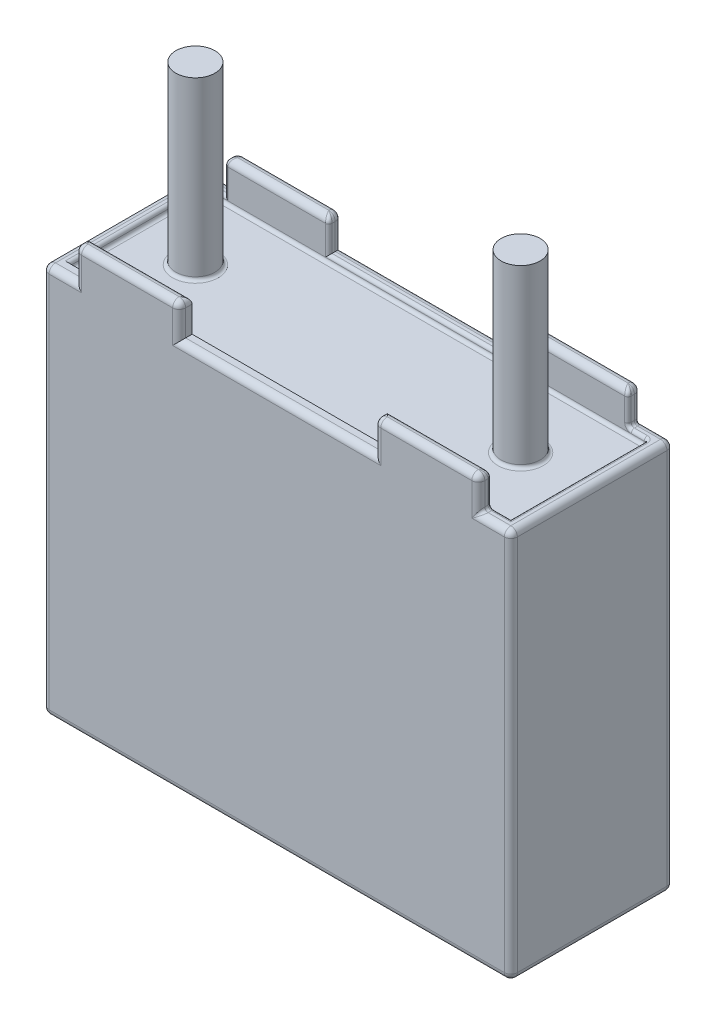
SolidWorks part; units mm, degrees
material "Sade Karbon Çeliği"
ref_plane "Ön Düzlem" through (0, 0, 0) normal (0, 0, 1) x (1, 0, 0)
ref_plane "Üst Düzlem" through (0, 0, 0) normal (0, 1, 0) x (1, 0, 0)
ref_plane "Sağ Düzlem" through (0, 0, 0) normal (1, 0, 0) x (0, 0, -1)
sketch "Çizim1" plane through (0, 0, 0) normal (0, 1, 0) x (1, 0, 0)
  line L1 (-3.6, -1.25) -> (3.6, -1.25)
  line L2 (-3.6, -1.25) -> (-3.6, 1.25)
  line L3 (-3.6, 1.25) -> (3.6, 1.25)
  line L4 (3.6, -1.25) -> (3.6, 1.25)
  line L5 (-3.6, -1.25) -> (3.6, 1.25) construction
  line L6 (-3.6, 1.25) -> (3.6, -1.25) construction
  point P0 (0, 0)
  dimension "D1" = 7.2
  dimension "D2" = 2.5
extrude "Тяло" add sketch "Çizim1" against normal blind 6.5
sketch "Çizim2" plane through (0, 0, 0) normal (0, 1, 0) x (1, 0, 0)
  line L0 (-3.6, 1.25) -> (-3.6, -1.25) construction
  line L1 (3.4, -1.05) -> (-3.4, -1.05)
  line L2 (3.4, -1.05) -> (3.4, 1.05)
  line L3 (3.4, 1.05) -> (-3.4, 1.05)
  line L4 (-3.4, -1.05) -> (-3.4, 1.05)
  line L5 (3.4, -1.05) -> (-3.4, 1.05) construction
  line L6 (3.4, 1.05) -> (-3.4, -1.05) construction
  line L7 (-3.6, -1.25) -> (3.6, -1.25) construction
  point P0 (0, 0)
  dimension "D1" = 0.2
  dimension "D2" = 0.2
extrude "Kes-Ekstrüzyon1" cut sketch "Çizim2" against normal blind 0.6
sketch "Çizim3" plane through (0, 0, 1.25) normal (0, 0, 1) x (1, 0, 0)
  line L2 (1.5, -0.5) -> (-1.5, -0.5)
  line L3 (1.5, -0.5) -> (1.5, 0)
  line L4 (-1.5, -0.5) -> (-1.5, 0)
  line L5 (1.5, 0) -> (-1.5, 0)
  line L7 (1.5, -0.5) -> (-1.5, 0) construction
  line L9 (-1.5, -0.5) -> (1.5, 0) construction
  line L10 (-3.6, 0) -> (3.6, 0) construction
  line L12 (-3.6, 0) -> (-3.1, 0)
  line L13 (-3.6, 0) -> (-3.6, -0.5)
  line L14 (-3.6, -0.5) -> (-3.1, -0.5)
  line L15 (-3.1, 0) -> (-3.1, -0.5)
  line L16 (3.6, 0) -> (3.1, 0)
  line L17 (3.6, 0) -> (3.6, -0.5)
  line L18 (3.6, -0.5) -> (3.1, -0.5)
  line L19 (3.1, 0) -> (3.1, -0.5)
  point P1 (0, -0.25)
  dimension "D1" = 0.5
  dimension "D2" = 3
  dimension "D3" = 0.5
extrude "Kes-Ekstrüzyon2" cut sketch "Çizim3" against normal blind 7
sketch "Çizim4" plane through (0, -0.6, 0) normal (0, 1, 0) x (-1, 0, 0)
  line L0 (-2.5, 0) -> (2.5, 0) construction
  circle A0 centre (-2.5, 0) radius 0.3
  circle A1 centre (2.5, 0) radius 0.3
  point P1 (0, 0)
  dimension "D1" = 5
  dimension "D2" = 0.6
extrude "Pin" add sketch "Çizim4" along normal blind 2.7
fillet "Radyus1" radius 0.1 40 edges at (0, -6.5, -1.25) (-3.6, -6.5, 0) (0, -6.5, 1.25) (3.6, -6.5, 0) (3.6, -0.5, 0) (-1.5, -0.25, 1.25) (0, -0.5, 1.25) (1.5, -0.25, 1.25) (3.1, -0.25, 1.25) (3.35, -0.5, 1.25) (3.6, -3.5, 1.25) (-3.35, -0.5, 1.25) (-3.1, -0.25, 1.25) (-3.6, -3.5, 1.25) (-3.6, -0.5, 0) (-3.35, -0.5, -1.25) (-3.6, -3.5, -1.25) (3.6, -3.5, -1.25) (3.35, -0.5, -1.25) (3.1, -0.25, -1.25) (1.5, -0.25, -1.25) (0, -0.5, -1.25) (-1.5, -0.25, -1.25) (-3.1, -0.25, -1.25) (-1.5, 0, 1.15) (-2.3, 0, 1.25) (-3.1, 0, 1.15) (-2.3, 0, 1.05) (3.1, 0, -1.15) (2.3, 0, -1.05) (1.5, 0, -1.15) (2.3, 0, -1.25) (3.1, 0, 1.15) (2.3, 0, 1.25) (1.5, 0, 1.15) (2.3, 0, 1.05) (-1.5, 0, -1.15) (-2.3, 0, -1.05) (-3.1, 0, -1.15) (-2.3, 0, -1.25)
fillet "Fillet1" radius 0.05 26 edges at (-2.5, -0.6, -0.3) (0, -0.6, -1.05) (3.4, -0.6, 0) (0, -0.6, 1.05) (-3.4, -0.6, 0) (2.5, -0.6, 0.3) (3.0707, -0.0293, 1.0793) (3.0707, -0.0293, -1.0793) (3.1, -0.3, 1.05) (3.1, -0.3, -1.05) (3.0707, -0.5293, -1.2207) (3.0707, -0.5293, 1.2207) (3.25, -0.5, 1.05) (3.4, -0.5, 0) (3.25, -0.5, -1.05) (3.1, -0.5, -1.1) (3.1, -0.5, 1.1) (-3.4, -0.5, 0) (-3.0707, -0.0293, -1.0793) (-1.5293, -0.0293, -1.0793) (1.5293, -0.0293, -1.0793) (-3.25, -0.5, -1.05) (-3.1, -0.3, -1.05) (-1.5, -0.3, -1.05) (0, -0.5, -1.05) (1.5, -0.3, -1.05)
